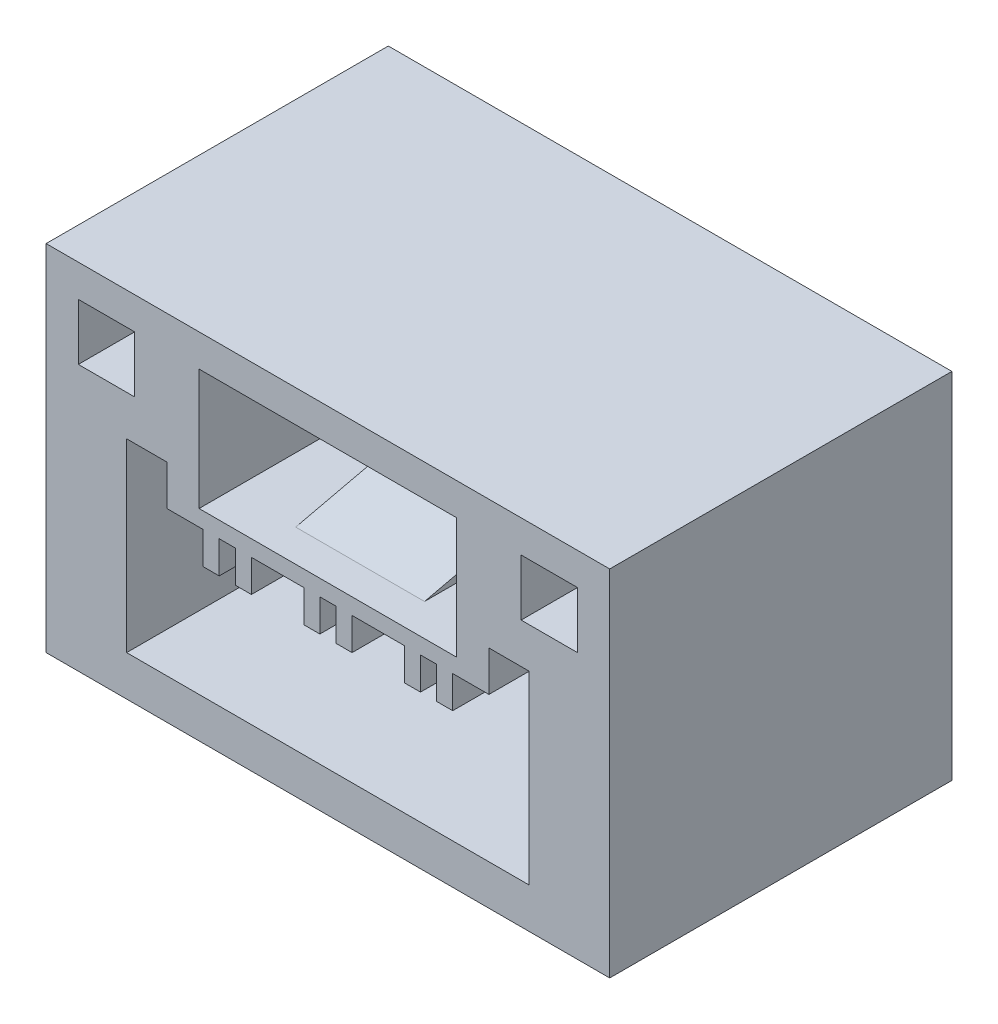
SolidWorks part; units mm, degrees
ref_plane "Front Plane" through (0, 0, 0) normal (0, 0, 1) x (1, 0, 0)
ref_plane "Top Plane" through (0, 0, 0) normal (0, 1, 0) x (1, 0, 0)
ref_plane "Right Plane" through (0, 0, 0) normal (1, 0, 0) x (0, 0, -1)
sketch "Sketch1" plane through (0, 0, 0) normal (0, 0, 1) x (1, 0, 0)
  line L0 (-2.5, 0.6) -> (-2.5, -1.7)
  line L1 (-3.5, 2.2) -> (3.5, 2.2)
  line L2 (-3.5, 2.2) -> (-3.5, -2.2)
  line L3 (-3.5, -2.2) -> (3.5, -2.2)
  line L4 (3.5, 2.2) -> (3.5, -2.2)
  line L5 (-3.5, 2.2) -> (3.5, -2.2) construction
  line L6 (-3.5, -2.2) -> (3.5, 2.2) construction
  line L7 (-3.1, 1.8) -> (-2.4, 1.8)
  line L8 (-3.1, 1.8) -> (-3.1, 1.1)
  line L9 (-3.1, 1.1) -> (-2.4, 1.1)
  line L10 (-2.4, 1.8) -> (-2.4, 1.1)
  line L11 (3.1, 1.8) -> (2.4, 1.8)
  line L12 (3.1, 1.8) -> (3.1, 1.1)
  line L13 (3.1, 1.1) -> (2.4, 1.1)
  line L14 (2.4, 1.8) -> (2.4, 1.1)
  line L15 (-2.5, -1.7) -> (2.5, -1.7)
  line L16 (2.5, -1.7) -> (2.5, 0.6)
  line L17 (2.5, 0.6) -> (2, 0.6)
  line L18 (2, 0.6) -> (2, 0.1)
  line L19 (2, 0.1) -> (-2, 0.1)
  line L20 (-2, 0.1) -> (-2, 0.6)
  line L21 (-2, 0.6) -> (-2.5, 0.6)
  line L23 (-1.6, 1.8) -> (1.6, 1.8)
  line L24 (-1.6, 1.8) -> (-1.6, 0.3)
  line L25 (-1.6, 0.3) -> (1.6, 0.3)
  line L26 (1.6, 1.8) -> (1.6, 0.3)
  point P0 (0, 0)
  point P21 (0, -1.7)
  point P23 (0, 0.1)
  point P24 (0, 1.8)
  dimension "D1" = 1
  dimension "D2" = 4.4
  dimension "B" = 7
  dimension "D3" = 0.5
  dimension "D4" = 0.5
  dimension "D5" = 1.6
  dimension "D6" = 0.7
  dimension "D7" = 0.4
  dimension "D8" = 0.4
  dimension "D9" = 0.4
  dimension "D10" = 0.4
  dimension "D11" = 1.9
  dimension "D12" = 0.2
extrude "Boss-Extrude1" add sketch "Sketch1" along normal blind 4.25
extrude "Boss-Extrude2" add sketch "Sketch1<2>" along normal blind 1 contours L11 L14 L13 L12 | L20 L21 L0 L15 L16 L17 L18 L19 | L10 L7 L8 L9 region at (0, -0.7395, 0) region at (-2.75, 1.45, 0) region at (2.75, 1.45, 0)
sketch "Sketch1<2>" plane through (0, 0, 0) normal (0, 0, 1) x (1, 0, 0) same geometry as "Sketch1"
sketch "Sketch3" plane through (0, 0, 0) normal (0, 0, 1) x (1, 0, 0)
  line L0 (1.15, 0.1) -> (1.35, 0.1) construction
  line L1 (0.95, 0.1) -> (1.15, 0.1)
  line L2 (0.95, 0.1) -> (0.95, -0.3)
  line L3 (0.95, -0.3) -> (1.15, -0.3)
  line L4 (1.15, 0.1) -> (1.15, -0.3)
  line L5 (1.35, 0.1) -> (1.55, 0.1)
  line L6 (1.35, 0.1) -> (1.35, -0.3)
  line L7 (1.35, -0.3) -> (1.55, -0.3)
  line L8 (1.55, 0.1) -> (1.55, -0.3)
  line L9 (2, 0.1) -> (-2, 0.1) construction
  line L10 (0, 4.5807) -> (0, -3.6561) construction
  point P13 (1.25, 0.1)
  dimension "D1" = 0.2
  dimension "D2" = 0.2
  dimension "D3" = 0.4
  dimension "A" = 2.5
extrude "Boss-Extrude3" add sketch "Sketch3" against normal up to surface (-1 mm away) from surface up to face at (0, -0.1, 1) starting at face at (0, 0, 4.25)
pattern_linear "LPattern1" count 3 spacing 1.25 along (-1, 0, 0) of "Boss-Extrude3"
sketch "Sketch4" plane through (0, 0, 0) normal (1, 0, 0) x (0, 0, -1)
  line L0 (-4.25, 0.3) -> (0, 0.3) construction
  line L1 (-4.25, 0.3) -> (0, 0.3)
  line L2 (-3.85, 0.3) -> (-2.125, 0.7)
  line L3 (-2.125, 0.7) -> (-2.125, 0.3)
  point P5 (-2.125, 0.3)
  dimension "D1" = 0.4
  dimension "D2" = 0.4
extrude "Boss-Extrude4" add sketch "Sketch4" along normal offset from surface 0.8 and the other way offset from surface 0.8 contours L3 L2 L1 region at (0, 0.4333, 2.7) up to face at (1.6, 1.05, 2.125) other way up to face at (-1.6, 1.05, 2.125)
